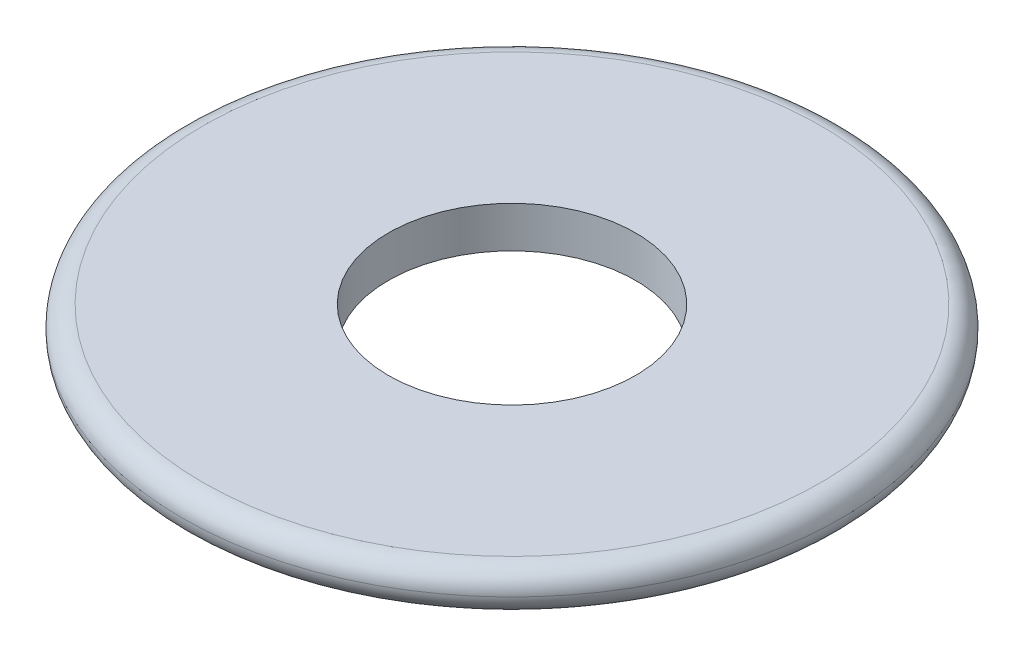
SolidWorks part; units mm, degrees
material "AISI 304"
ref_plane "Front" through (0, 0, 0) normal (0, 0, 1) x (1, 0, 0)
ref_plane "Top" through (0, 0, 0) normal (0, 1, 0) x (1, 0, 0)
ref_plane "Right" through (0, 0, 0) normal (1, 0, 0) x (0, 0, -1)
sketch "草图1" plane through (0, 0, 0) normal (0, 1, 0) x (1, 0, 0)
  circle A0 centre (0, 0) radius 3
  circle A1 centre (0, 0) radius 8
  dimension "垫圈内径" = 6
  dimension "垫圈外径" = 16
extrude "凸台-拉伸1" add sketch "草图1" along normal mid plane 1
fillet "圆角1" radius 0.5 2 edges at (0, -0.5, 8) (0, 0.5, 8)
other "冻结***"
move or copy body "Body-Move/Copy1" [suppressed] bodies to move or copy 101
